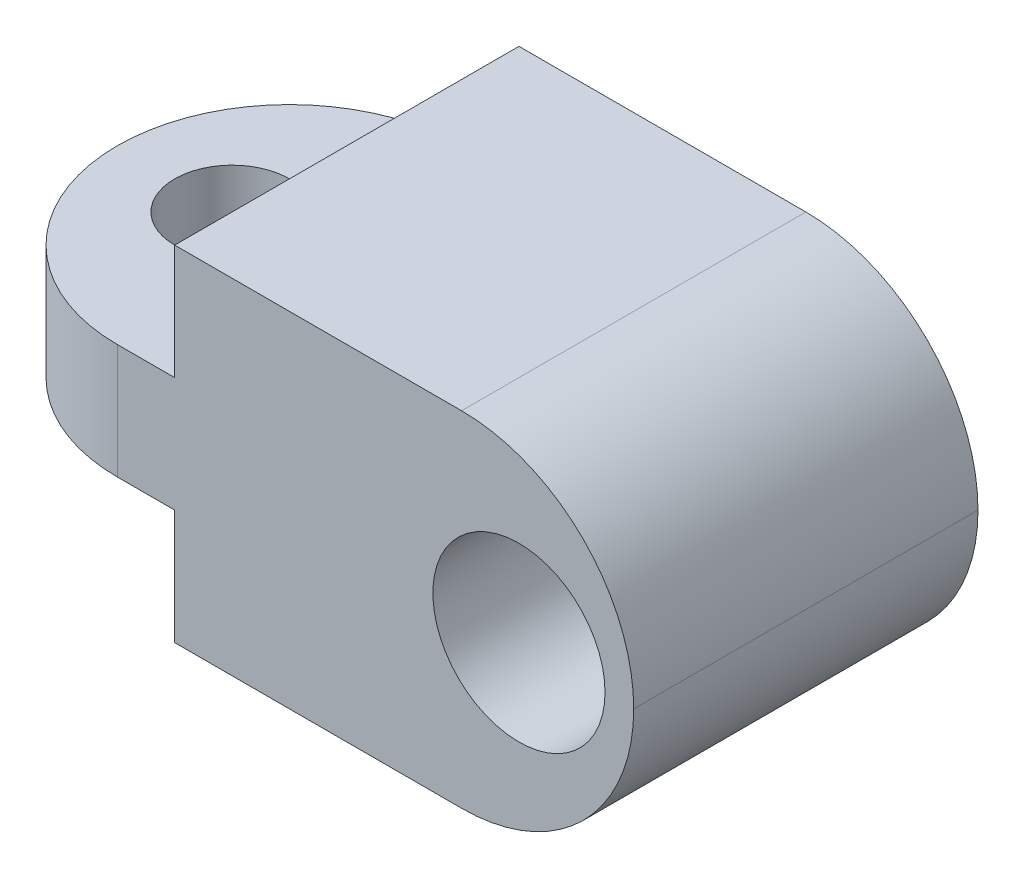
SolidWorks part; units mm, degrees
ref_plane "Alzado" through (0, 0, 0) normal (0, 0, 1) x (1, 0, 0)
ref_plane "Planta" through (0, 0, 0) normal (0, 1, 0) x (1, 0, 0)
ref_plane "Vista lateral" through (0, 0, 0) normal (1, 0, 0) x (0, 0, -1)
sketch "Croquis4" plane through (0, 0, 0) normal (0, 0, 1) x (1, 0, 0)
  line L1 (-60, -30) -> (60, -30)
  line L2 (-60, -30) -> (-60, 30)
  line L3 (-60, 30) -> (60, 30)
  line L4 (60, -30) -> (60, 30)
  line L5 (-60, -30) -> (60, 30) construction
  line L6 (-60, 30) -> (60, -30) construction
  point P0 (0, 0)
extrude "Saliente-Extruir3" add sketch "Croquis4" along normal blind 60
fillet "Redondeo1" radius 30 2 edges at (60, -30, 30) (60, 30, 30)
sketch "Croquis5" plane through (0, 0, 0) normal (0, 0, 1) x (1, 0, 0)
  line L1 (-60, 30) -> (-20, 30)
  line L2 (-60, 30) -> (-60, 10)
  line L3 (-60, 10) -> (-20, 10)
  line L4 (-20, 30) -> (-20, 10)
  line L5 (-60, -30) -> (-20, -30)
  line L6 (-60, -30) -> (-60, -10)
  line L7 (-60, -10) -> (-20, -10)
  line L8 (-20, -30) -> (-20, -10)
extrude "Cortar-Extruir1" cut sketch "Croquis5" along normal blind 60
sketch "Croquis6" plane through (0, 0, 0) normal (0, 1, 0) x (1, 0, 0)
  circle A0 centre (-40, -30) radius 10
extrude "Cortar-Extruir2" cut sketch "Croquis6" against normal blind 10 and the other way blind 10
fillet "Redondeo2" radius 30 2 edges at (-60, 0, 60) (-60, 0, 0)
sketch "Croquis8" plane through (0, 0, 0) normal (0, 0, 1) x (1, 0, 0)
  line L2 (-20, 30) -> (-20, 10)
  line L6 (-20, -10) -> (-20, -30)
  circle A0 centre (40, 0) radius 15
  point P14 (0, 0)
extrude "Cortar-Extruir3" cut sketch "Croquis8" along normal blind 60 contours A0
